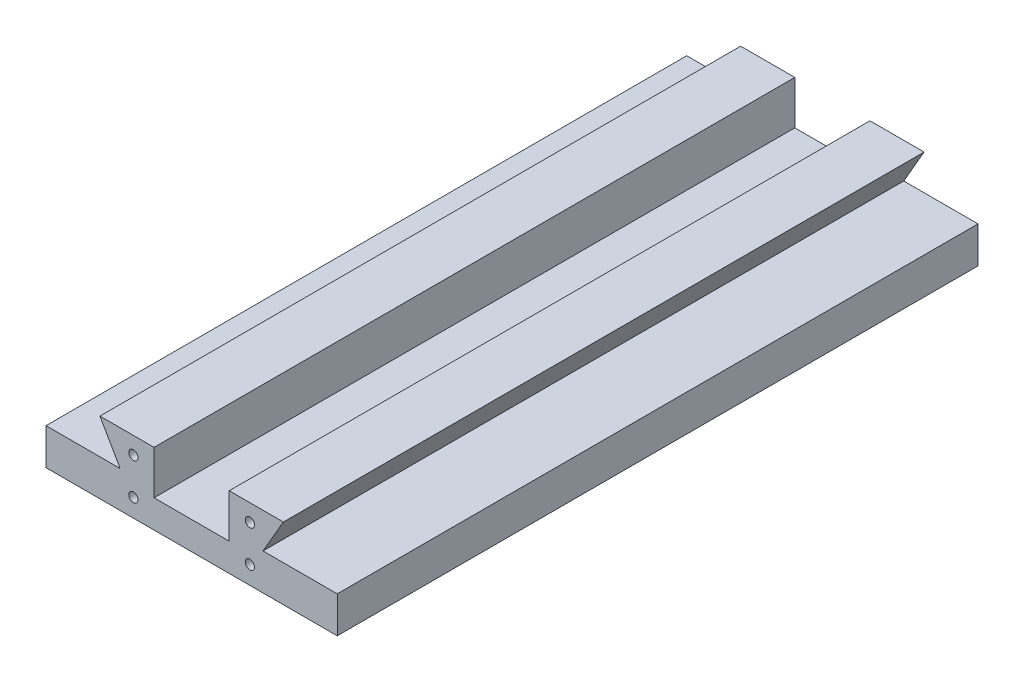
SolidWorks part; units mm, degrees
material "Ductile Iron"
ref_plane "Front Plane" through (0, 0, 0) normal (0, 0, 1) x (1, 0, 0)
ref_plane "Top Plane" through (0, 0, 0) normal (0, 1, 0) x (1, 0, 0)
ref_plane "Right Plane" through (0, 0, 0) normal (1, 0, 0) x (0, 0, -1)
sketch "Sketch6" plane through (0, 0, 0) normal (0, 0, 1) x (1, 0, 0)
  line B0 (-63.5, 0) -> (63.5, 0)
  line B1 (63.5, 0) -> (63.5, 15.875)
  line B2 (63.5, 15.875) -> (38.4596, 15.875)
  line B3 (38.4596, 15.875) -> (47.625, 31.75)
  line B4 (47.625, 31.75) -> (16.0563, 31.75)
  line B5 (-40.2927, 31.75) -> (-31.1272, 15.875)
  line B6 (-31.1272, 15.875) -> (-63.5, 15.875)
  line B7 (-63.5, 15.875) -> (-63.5, 0)
  line B8 (-38.4596, 15.875) -> (-47.625, 31.75)
  line B9 (-16.0563, 31.75) -> (-16.0563, 12.7) construction
  line B10 (-16.0563, 12.7) -> (16.0563, 12.7) construction
  line B11 (16.0563, 12.7) -> (16.0563, 31.75) construction
  line B12 (-16.0563, 31.75) -> (-40.2927, 31.75)
  line B13 (-63.5, 15.875) -> (-63.5, 47.625)
  line B14 (-63.5, 47.625) -> (63.5, 47.625)
  line B15 (63.5, 47.625) -> (63.5, 15.875)
  line B16 (-16.0563, 31.75) -> (16.0563, 31.75) construction
  line B17 (0, 47.625) -> (0, 0) construction
  line B18 (-38.4596, 15.875) -> (38.4596, 15.875) construction
  line B19 (-28.702, 36.957) -> (28.702, 36.957) construction
  line B20 (-25.4, 7.874) -> (25.4, 7.874) construction
  line B21 (-25.4, 7.874) -> (-25.4, 23.8125) construction
  line B22 (25.4, 7.874) -> (25.4, 23.8125) construction
  line B23 (-52.832, 23.8125) -> (52.832, 23.8125) construction
  circle B24 centre (0, 22.225) radius 18.669 construction
  line B25 (40.2927, 31.75) -> (31.1272, 15.875)
  line B26 (31.1272, 15.875) -> (38.4596, 15.875)
  line B27 (-15.875, 31.75) -> (-15.875, 12.7)
  line B28 (-16.0563, 31.75) -> (-15.875, 31.75)
  line B29 (-15.875, 12.7) -> (15.875, 12.7)
  line B30 (15.875, 12.7) -> (15.875, 31.75)
  line B31 (15.875, 31.75) -> (16.0563, 31.75)
sketch_block_instance "dovetail pair-2"
sketch_block "dovetail pair" parameters "D8"=37.338, "D1"=60, "D2"=127, "D3"=6.35, "D4"=15.875, "D5"=31.75, "D6"=95.25, "D7"=19.05, "D9"=60, "D10"=31.75, "D11"=50.8, "D12"=23.876, "D13"=7.874, "D14"=10.668, "D15"=34.798, "D16"=21.082, "D17"=7.9375, "D18"=24.4437
sketch "dovetail-male-profile" plane through (0, 0, 0) normal (0, 0, 1) x (1, 0, 0)
  line L0 (39.9994, 31.242) -> (16.383, 31.242)
  line L1 (-16.383, 31.242) -> (-39.9994, 31.242)
  line L2 (16.383, 31.242) -> (16.383, 12.192)
  line L3 (16.383, 12.192) -> (-16.383, 12.192)
  line L4 (-16.383, 12.192) -> (-16.383, 31.242)
  line L5 (0, 47.625) -> (0, 0) construction
  line L6 (31.1272, 15.875) -> (38.4596, 15.875) construction
  line L7 (63.5, 15.875) -> (38.4596, 15.875) construction
  line L8 (63.5, 0) -> (63.5, 15.875) construction
  line L9 (-63.5, 0) -> (63.5, 0) construction
  line L10 (-63.5, 15.875) -> (-63.5, 0) construction
  line L11 (-31.1272, 15.875) -> (-63.5, 15.875) construction
  line L13 (-31.1272, 15.875) -> (-39.9994, 31.242)
  line L14 (31.1272, 15.875) -> (38.4596, 15.875)
  line L15 (63.5, 15.875) -> (38.4596, 15.875)
  line L16 (63.5, 0) -> (63.5, 15.875)
  line L17 (-63.5, 0) -> (63.5, 0)
  line L18 (-63.5, 15.875) -> (-63.5, 0)
  line L19 (-31.1272, 15.875) -> (-63.5, 15.875)
  line L20 (-40.2927, 31.75) -> (-31.1272, 15.875) construction
  line L21 (31.1272, 15.875) -> (39.9994, 31.242)
  line L22 (40.2927, 31.75) -> (31.1272, 15.875) construction
  line L23 (47.625, 31.75) -> (16.0563, 31.75) construction
  line L25 (-16.0563, 12.7) -> (16.0563, 12.7) construction
  line L27 (15.875, 12.7) -> (15.875, 31.75) construction
  point P23 (0, 12.192)
  dimension "D2" = 0.508
  dimension "D1" = 0.508
  dimension "D3" = 0.508
extrude "x-guide-extrude" add sketch "dovetail-male-profile" along normal blind 279.4 contours L14 L21 L0 L2 L3 L4 L1 L13 L19 L18 L17 L16 L15 region at (0, 11.4877, 0)
hole_wizard "end plate holes" positions "Sketch2" profile "Sketch3" tap size "#10-32" standard "ANSI Inch"
sketch "Sketch2" plane through (0, 0, 0) normal (0, 0, -1) x (-1, 0, 0)
  point P27 (-25.4, 23.8125)
  point P29 (25.4, 23.8125)
  point P31 (25.4, 7.874)
  point P33 (-25.4, 7.874)
sketch "Sketch3" plane through (25.4, 23.8125, 0) normal (1, 0, 0) x (0, 1, 0)
  line L0 (0, 0) -> (0, 13.1513)
  line L1 (0, 13.1513) -> (2.0193, 11.938)
  line L2 (2.0193, 11.938) -> (2.0193, 0)
  line L3 (2.0193, 0) -> (0, 0)
  line L4 (0, 13.1513) -> (-2.0193, 11.938) construction
  line L5 (0, -6.35) -> (0, 107.95) construction
  dimension "Tap Drill Dia." = 4.0386
  dimension "Tap Drill Depth" = 11.938
  dimension "Drill Angle" = 118
cosmetic thread "Hole Thread1" parameters "D1"=9.652, "D2"=4.826
cosmetic thread "Hole Thread2" parameters "D1"=9.652, "D2"=4.826
cosmetic thread "Hole Thread9" parameters "D1"=9.652, "D2"=4.826
cosmetic thread "Hole Thread10" parameters "D1"=9.652, "D2"=4.826
hole_wizard "end plate holes 2" positions "Sketch4" profile "Sketch5" tap size "#10-32" standard "ANSI Inch"
sketch "Sketch4" plane through (0, 0, 279.4) normal (0, 0, 1) x (1, 0, 0)
  point P8 (25.4, 23.8125)
  point P10 (25.4, 7.874)
  point P12 (-25.4, 7.874)
  point P14 (-25.4, 23.8125)
cosmetic thread "Hole Thread5" parameters "D1"=9.652, "D2"=4.826
cosmetic thread "Hole Thread6" parameters "D1"=9.652, "D2"=4.826
cosmetic thread "Hole Thread11" parameters "D1"=9.652, "D2"=4.826
cosmetic thread "Hole Thread12" parameters "D1"=9.652, "D2"=4.826
sketch "Sketch5" plane through (25.4, 23.8125, 279.4) normal (1, 0, 0) x (0, -1, 0)
  line L0 (0, 0) -> (0, 13.1513)
  line L1 (0, 13.1513) -> (2.0193, 11.938)
  line L2 (2.0193, 11.938) -> (2.0193, 0)
  line L5 (2.0193, 0) -> (0, 0)
  line L10 (0, 13.1513) -> (-2.0193, 11.938) construction
  line L11 (0, -6.35) -> (0, 107.95) construction
  dimension "Tap Drill Dia." = 4.0386
  dimension "Tap Drill Depth" = 11.938
  dimension "Drill Angle" = 118
equation "\"dovetail-angle\" = 60"
equation "\"dovetail-stock-width\" = 5"
equation "\"dovetail-stock-height\" = 1.25"
equation "\"dovetail-throat-width\" = \"dovetail-stock-width\" - (2 * \"dovetail-depth\")"
equation "\"dovetail-depth\" = 0.5 * \"dovetail-stock-height\""
equation "\"delta-x\" = 6"
equation "\"delta-y\" = 3"
equation "\"gib-thickness\" = 0.25"
equation "\"x-slide-length\" = \"dovetail-stock-width\" + \"delta-x\""
equation "\"y-slide-length\" = \"dovetail-stock-width\" + \"delta-y\""
equation "\"D1@x-guide-extrude\"=\"x-slide-length\""
equation "\"dog-point-diam\" = .149"
equation "\"dog-point-length\" = .067"
equation "\"dovetail-double-height\" = 2 * \"dovetail-depth\" + 0.5"
equation "\"acme-major-diam\" = .5"
equation "\"acme-pitch-diam\" = 0.45"
equation "\"acme-minor-diam\" = 0.4"
equation "\"acme-nut-od\" = 1.47"
equation "\"acme-nut-length\" = 1"
equation "\"acme-nut-trim-height\" = .75"
equation "\"screw-bearing-od\" = 0.5"
equation "\"screw-bearing-length\" = .375"
equation "\"end-plate-thickness\" = \"screw-bearing-length\""
equation "\"screw-bearing-id\" = .3125"
equation "\"screw-add-length\" = 2 * \"end-plate-thickness\" + 1 + 0.5"
equation "\"acme-nut-mount-hole-space-horz\" = 0.95"
equation "\"acme-nut-mount-hole-space-vert\" = 0.5 * \"acme-nut-length\""
equation "\"x-screw-length\" = \"x-slide-length\" + \"screw-add-length\""
equation "\"y-screw-length\" = \"y-slide-length\" + \"screw-add-length\""
equation "\"D2@dovetail pair\"=\"dovetail-stock-width\""
equation "\"D1@dovetail pair\"=\"dovetail-angle\""
equation "\"D3@dovetail pair\"=\"gib-thickness\""
equation "\"D4@dovetail pair\"=\"dovetail-depth\""
equation "\"D5@dovetail pair\"=\"dovetail-stock-height\""
equation "\"D6@dovetail pair\"=\"dovetail-throat-width\""
equation "\"D10@dovetail pair\"=\"dovetail-stock-height\""
equation "\"D7@dovetail pair\"=\"acme-nut-trim-height\""
equation "\"D8@dovetail pair\"=\"acme-nut-od\""
equation "\"D9@dovetail pair\"=\"dovetail-angle\""
equation "\"D17@dovetail pair\"=\"dovetail-depth\"/2"
equation "\"acme-nut-trim-width\" = 1.25"
equation "\"vise-hole-center-dist\" = 6.75"
equation "\"wiper_plate_clearance\" = .03"
equation "\"dial-width\" = 0.5"
equation "\"quarter-twenty-free-fit\" = .2667"
equation "\"acme_nut_clearance\" = .02"
equation "\"dovetail_male_clearance\" = .02"
equation "\"D1@dovetail-male-profile\"=\"dovetail_male_clearance\""
equation "\"D2@dovetail-male-profile\"=\"dovetail_male_clearance\""
equation "\"D3@dovetail-male-profile\"=\"dovetail_male_clearance\""
